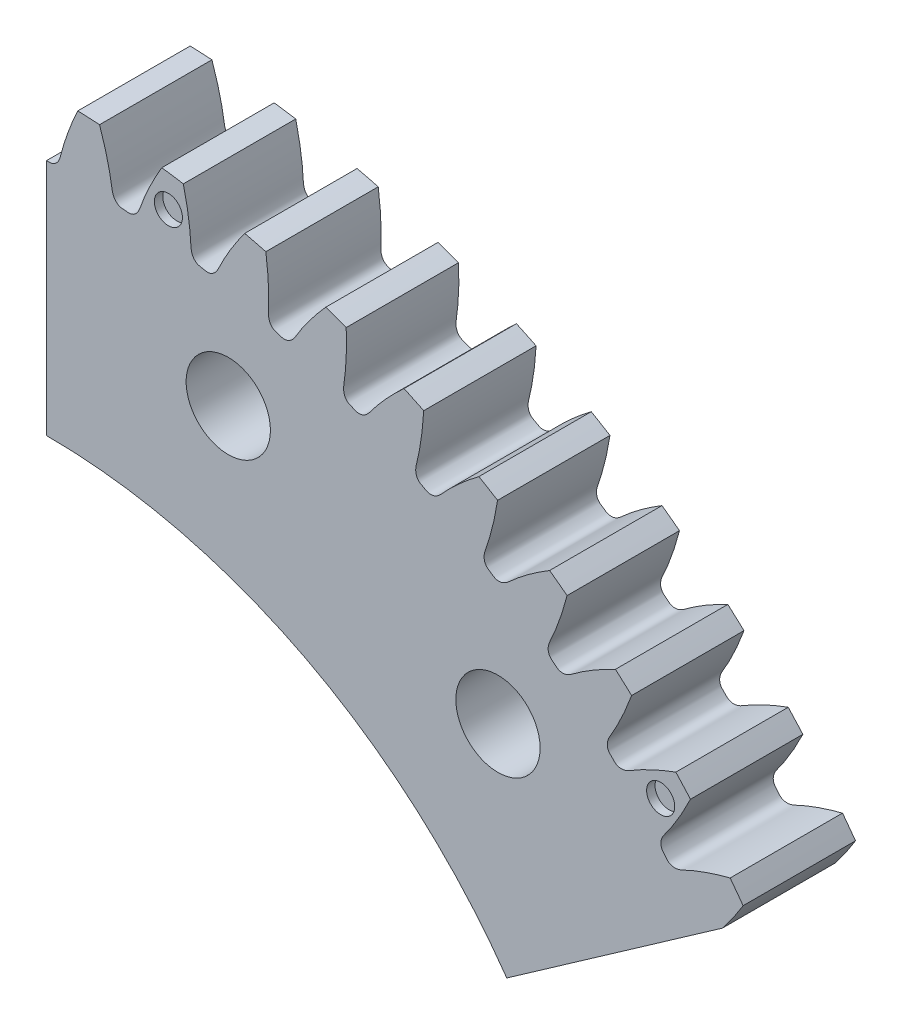
SolidWorks part; units mm, degrees
material "Д16 ГОСТ 4784-97"
ref_plane "FRONT" through (0, 0, 0) normal (0, 0, 1) x (1, 0, 0)
ref_plane "TOP" through (0, 0, 0) normal (0, 1, 0) x (1, 0, 0)
ref_plane "RIGHT" through (0, 0, 0) normal (1, 0, 0) x (0, 0, -1)
ref_axis "Ось1" through (0, 0, 50) along (0, 0, -1)
sketch "SketchRevolveSpurAssemblyNew1Gear" plane through (0, 0, 0) normal (1, 0, 0) x (0, 0, -1)
  line L0 (0, 0) -> (1, 0) construction
  line L1 (-4, 0) -> (-4, 30.5859)
  line L2 (-4, 30.5859) -> (0, 30.5859)
  line L3 (0, 30.5859) -> (0, 0)
  line L4 (0, 0) -> (-4, 0)
  dimension "D1" = 4
revolve "SpurAssemblyNew1Gear" add sketch "SketchRevolveSpurAssemblyNew1Gear" angle 360 about L0
sketch "SketchToothSpurAssemblyNew1Gear" plane through (0, 0, 0) normal (0, 0, 1) x (1, 0, 0)
  arc A0 (30.5945, 1.1268) -> (30.5945, -1.1268) centre (0, 0) cw
  spline S0 degree 3 poles (30.5945, -1.1268) (30.5132, -1.0888) (30.3922, -1.0339) (30.2321, -0.9645) (30.1166, -0.9161) (30.0041, -0.8705) (29.8946, -0.8275) (29.7881, -0.7872) (29.6848, -0.7494) (29.5845, -0.7141) (29.4875, -0.6811) (29.3937, -0.6505) (29.3032, -0.6221) (29.216, -0.5958) (29.1321, -0.5716) (29.0516, -0.5494) (28.953, -0.523) (28.873, -0.505) (28.8129, -0.4861) (28.7913, -0.4788) (28.7701, -0.4709) (28.7493, -0.4625) (28.7287, -0.4535) (28.7084, -0.4437) (28.6882, -0.4331) (28.6681, -0.4215) (28.648, -0.4087) (28.6279, -0.3944) (28.6078, -0.3785) (28.5876, -0.3604) (28.5676, -0.3397) (28.5479, -0.3161) (28.529, -0.289) (28.5115, -0.2581) (28.4964, -0.2233) (28.4848, -0.1848) (28.478, -0.1456) (28.4749, -0.0836) (28.4778, 0) (28.4749, 0.0836) (28.478, 0.1456) (28.4848, 0.1848) (28.4964, 0.2233) (28.5115, 0.2581) (28.529, 0.289) (28.5479, 0.3161) (28.5676, 0.3397) (28.5876, 0.3604) (28.6078, 0.3785) (28.6279, 0.3944) (28.648, 0.4087) (28.6681, 0.4215) (28.6882, 0.4331) (28.7084, 0.4437) (28.7287, 0.4535) (28.7493, 0.4625) (28.7701, 0.4709) (28.7913, 0.4788) (28.8129, 0.4861) (28.873, 0.505) (28.953, 0.523) (29.0516, 0.5494) (29.1321, 0.5716) (29.216, 0.5958) (29.3032, 0.6221) (29.3937, 0.6505) (29.4875, 0.6811) (29.5845, 0.7141) (29.6848, 0.7494) (29.7881, 0.7872) (29.8946, 0.8275) (30.0041, 0.8705) (30.1166, 0.9161) (30.2321, 0.9645) (30.3922, 1.0339) (30.5132, 1.0888) (30.5945, 1.1268) knots 0 0 0 0 0.052869 0.078188 0.102762 0.126592 0.149678 0.172019 0.193617 0.21447 0.234579 0.253943 0.272564 0.29044 0.307572 0.32396 0.339603 0.367681 0.372205 0.376674 0.381103 0.385507 0.389906 0.394324 0.398788 0.403329 0.407986 0.412802 0.417828 0.423121 0.428742 0.434755 0.441216 0.448165 0.45561 0.463513 0.471776 0.478976 0.5 0.521024 0.528224 0.536487 0.54439 0.551835 0.558784 0.565245 0.571258 0.576879 0.582172 0.587198 0.592014 0.596671 0.601212 0.605676 0.610094 0.614493 0.618897 0.623326 0.627795 0.632319 0.660397 0.67604 0.692428 0.70956 0.727436 0.746057 0.765421 0.78553 0.806383 0.827981 0.850322 0.873408 0.897238 0.921812 0.947131 1 1 1 1
extrude "ToothExtrudeCutSpurAssemblyNew1Gear" cut sketch "SketchToothSpurAssemblyNew1Gear" against normal blind 4 and the other way blind 4
pattern_circular "PatternSpurAssemblyNew1Gear" count 64 every 5.625 about axis through (0, 0, 50) along (0, 0, -1) of "ToothExtrudeCutSpurAssemblyNew1Gear"
sketch "AuxiliarySketchSpurAssemblyNew1Gear" plane through (0, 0, 0) normal (0, 0, 1) x (1, 0, 0)
  circle A0 centre (0, 0) radius 30 construction
  circle A1 centre (0, 0) radius 28.1908 construction
  circle A2 centre (0, 0) radius 28.8965 construction
  circle A3 centre (0, 0) radius 30.5859 construction
  circle A4 centre (0, 0) radius 28.4766 construction
  dimension "PitchDiameter" = 60
  dimension "BaseDiameter" = 56.3816
  dimension "FormDiameter" = 57.7931
  dimension "MajorDiameter" = 61.1719
  dimension "MinorDiameter" = 56.9531
sketch "Эскиз1" plane through (0, 0, 4) normal (0, 0, 1) x (1, 0, 0)
  line L0 (0, 0) -> (0, 39.1523) construction
  line L1 (0, 0) -> (32.0717, 22.4569) construction
  line L2 (0, 0) -> (10.3053, 38.46) construction
  line L3 (0, 0) -> (25.248, 30.0894) construction
  line L4 (0, 20) -> (0, 39.1523)
  line L5 (16.383, 11.4715) -> (32.0717, 22.4569)
  arc A0 (0, 39.1523) -> (32.0717, 22.4569) centre (0, 0) ccw
  circle A1 centre (0, 0) radius 25 construction
  circle A2 centre (6.4705, 24.1481) radius 1.5
  circle A3 centre (16.0697, 19.1511) radius 1.5
  arc A4 (16.383, 11.4715) -> (0, 20) centre (0, 0) ccw
  dimension "D1" = 55
  dimension "D2" = 15
  dimension "D3" = 25
  dimension "D4" = 3
  dimension "D5" = 3
  dimension "D6" = 50
  dimension "D7" = 20
extrude "Вырез-Вытянуть1" cut sketch "Эскиз1" against normal through all
sketch "Эскиз2" plane through (0, 0, 4) normal (0, 0, 1) x (1, 0, 0)
  circle A0 centre (0, 0) radius 29.4575 construction
  circle A1 centre (4.3381, 29.1363) radius 0.5
  circle A2 centre (21.8606, 19.7448) radius 0.5
extrude "Вырез-Вытянуть6" cut sketch "Эскиз2" against normal blind 0.3
